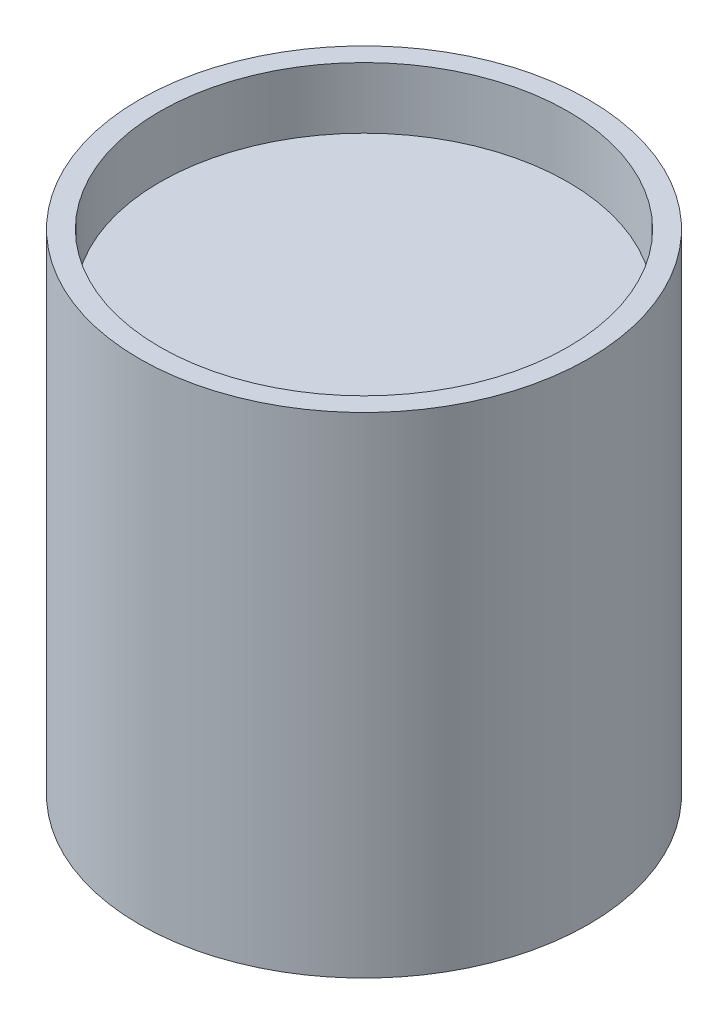
SolidWorks part; units mm, degrees
material "Glass"
ref_plane "Front Plane" through (0, 0, 0) normal (0, 0, 1) x (1, 0, 0)
ref_plane "Top Plane" through (0, 0, 0) normal (0, 1, 0) x (1, 0, 0)
ref_plane "Right Plane" through (0, 0, 0) normal (1, 0, 0) x (0, 0, -1)
sketch "Sketch1" plane through (0, 0, 0) normal (0, 0, 1) x (1, 0, 0)
  line L0 (0, -1000) -> (0, 49000) construction
  line L1 (31.75, 76.2) -> (31.75, 3.175)
  line L2 (31.75, 3.175) -> (0, 3.175)
  line L3 (0, 3.175) -> (0, 0)
  line L4 (0, 0) -> (34.925, 0)
  line L5 (34.925, 0) -> (34.925, 76.2)
  line L6 (34.925, 76.2) -> (31.75, 76.2)
  dimension "D1" = 76.2
  dimension "D2" = 69.85
  dimension "D3" = 3.175
  dimension "D4" = 3.175
revolve "Revolve1" add sketch "Sketch1" angle 360 about L0
sketch "Sketch2" plane through (0, 0, 0) normal (0, 0, 1) x (1, 0, 0)
  line L0 (0, 3.2004) -> (31.7246, 3.2004)
  line L1 (31.7246, 3.2004) -> (31.7246, 66.7004)
  line L2 (31.7246, 66.7004) -> (0, 66.7004)
  line L3 (0, 66.7004) -> (0, 3.2004)
  line L4 (-34.925, 0) -> (34.925, 0) construction
  dimension "D1" = 3.2004
  dimension "D2" = 31.7246
  dimension "D3" = 63.5
revolve "Revolve2" add sketch "Sketch2" angle 360 about L3
